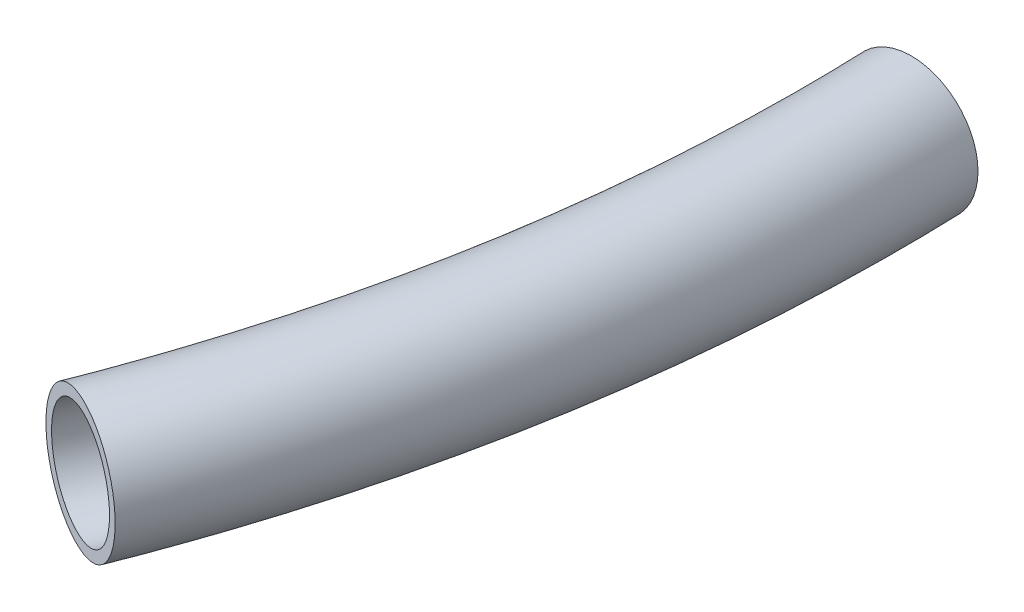
SolidWorks part; units mm, degrees
ref_plane "Front Plane" through (0, 0, 0) normal (0, 0, 1) x (1, 0, 0)
ref_plane "Top Plane" through (0, 0, 0) normal (0, 1, 0) x (1, 0, 0)
ref_plane "Right Plane" through (0, 0, 0) normal (1, 0, 0) x (0, 0, -1)
sketch "Sketch1" plane through (0, 0, 0) normal (0, 0, 1) x (1, 0, 0)
  circle A0 centre (0, 0) radius 0.622
  circle A1 centre (0, 0) radius 0.5206
  dimension "D1" = 1.244
  dimension "D2" = 1.0412
sketch "Sketch2" plane through (0, 0, 0) normal (0, 1, 0) x (1, 0, 0)
  line L0 (-1.2807, -5.2181) -> (-0.4359, -5.5303)
  line L1 (0.6186, 0) -> (-0.6174, 0)
  line L2 (-0.3594, 0) -> (-0.3594, 0.955)
  line L4 (-0.9159, -3.7446) -> (-0.0308, -3.9603)
  line L5 (-0.6889, -2.2259) -> (0.2332, -2.3491)
  line L6 (0.1626, -2.8371) -> (-0.7475, -2.7262)
  line L7 (-0.5001, 0.955) -> (-0.5001, 0)
  line L8 (-0.6186, -1.2203) -> (0.293, -1.2203)
  line L9 (-0.3594, 0.955) -> (-0.5001, 0.955)
  line L10 (-1.0137, -4.2027) -> (-0.1397, -4.4401)
  line L11 (-0.622, 0) -> (0.622, 0) construction
  line L12 (-0.622, 0) -> (0.622, 0) construction
  line L13 (-1.2807, -5.2181) -> (-1.863, -6.8482) construction
  line L14 (-1.0849, -7.6927) -> (-0.5001, 2.9608) construction
  line L17 (-0.5608, -6.8714) -> (-1.6957, -6.4327)
  arc A0 (-0.4359, -5.5303) -> (-0.1397, -4.4401) centre (-16.4821, -0.5853) ccw
  arc A1 (-1.2807, -5.2181) -> (-1.6957, -6.4327) centre (-16.799, -0.5942) cw
  arc A2 (-0.0308, -3.9603) -> (0.1626, -2.8371) centre (-6.8828, -2.2023) ccw
  arc A3 (-0.5608, -2.243) -> (-0.496, -1.2203) centre (-14.6135, -0.839) ccw
  arc A4 (0.2332, -2.3491) -> (0.293, -1.2203) centre (-7.2506, -1.3866) ccw
  arc A5 (-1.0849, -5.2905) -> (-0.7892, -4.2637) centre (-15.1503, -0.6836) ccw
  arc A6 (-0.6889, -2.2259) -> (-0.7475, -2.7262) centre (-16.799, -0.5942) cw
  arc A7 (0.6186, 0) -> (-0.5608, -6.8714) centre (-16.5098, -0.597) cw
  arc A8 (-0.6818, -3.8017) -> (-0.4956, -2.7569) centre (-15.1503, -0.6836) ccw
  arc A9 (-1.1971, -5.249) -> (-0.9046, -4.2323) centre (-14.6135, -0.839) ccw
  arc A10 (-0.6174, 0) -> (-0.6186, -1.2203) centre (-16.799, -0.5942) cw
  arc A11 (-0.9159, -3.7446) -> (-1.0137, -4.2027) centre (-16.799, -0.5942) cw
  arc A12 (-0.799, -3.7731) -> (-0.6196, -2.7418) centre (-14.6135, -0.839) ccw
  arc A13 (-0.4338, -2.26) -> (-0.3594, -1.2203) centre (-15.1503, -0.6836) ccw
  point P44 (0.5831, 0)
sketch "Sketch5" plane through (0, 0, 0) normal (0, 1, 0) x (1, 0, 0)
  line L8 (0.2332, -2.3491) -> (-0.6889, -2.2259)
  line L9 (-0.6186, -1.2203) -> (0.293, -1.2203)
  line L10 (0.6186, 0) -> (-0.6174, 0)
  line L11 (-1.6957, -6.4327) -> (-0.5608, -6.8714)
  line L12 (-0.4359, -5.5303) -> (-1.2807, -5.2181)
  line L13 (-1.0137, -4.2027) -> (-0.1397, -4.4401)
  line L14 (-0.0308, -3.9603) -> (-0.9159, -3.7446)
  line L15 (-0.7475, -2.7262) -> (0.1626, -2.8371)
  line L17 (-1.6957, -6.4327) -> (-0.5608, -6.8714)
  arc A8 (0.2332, -2.3491) -> (0.293, -1.2203) centre (-7.2506, -1.3866) ccw
  arc A9 (-0.6186, -1.2203) -> (-0.6174, 0) centre (-16.799, -0.5942) ccw
  arc A10 (-0.5608, -6.8714) -> (0.6186, 0) centre (-16.5098, -0.597) ccw
  arc A11 (-1.6957, -6.4327) -> (-1.2807, -5.2181) centre (-16.799, -0.5942) ccw
  arc A12 (-0.4359, -5.5303) -> (-0.1397, -4.4401) centre (-16.4821, -0.5853) ccw
  arc A13 (-1.0137, -4.2027) -> (-0.9159, -3.7446) centre (-16.799, -0.5942) ccw
  arc A14 (-0.0308, -3.9603) -> (0.1626, -2.8371) centre (-6.8828, -2.2023) ccw
  arc A15 (-0.7475, -2.7262) -> (-0.6889, -2.2259) centre (-16.799, -0.5942) ccw
  arc A18 (-0.5608, -6.8714) -> (0.6186, 0) centre (-16.5098, -0.597) ccw
  dimension "D1" = 0
sweep "Sweep2" add profiles "Sketch1" path "Sketch2"
sketch "Sketch7" plane through (0, 0, 0) normal (0, 1, 0) x (1, 0, 0)
  line L3 (-1.2807, -5.2181) -> (-1.4555, -5.1535)
  line L4 (-1.4555, -5.1535) -> (-1.1748, -4.1203)
  line L5 (-1.1748, -4.1203) -> (-1.0137, -4.2027)
  line L6 (-0.9159, -3.7446) -> (-1.1749, -3.6815)
  line L7 (-1.1749, -3.6815) -> (-1.0177, -2.665)
  line L8 (0.2332, -2.3491) -> (-0.6889, -2.2259)
  line L9 (-0.6186, -1.2203) -> (0.293, -1.2203)
  line L10 (0.6186, 0) -> (-0.6174, 0)
  line L11 (-1.6957, -6.4327) -> (-0.5608, -6.8714)
  line L12 (-0.4359, -5.5303) -> (-1.2807, -5.2181)
  line L13 (-1.0137, -4.2027) -> (-0.1397, -4.4401)
  line L14 (-0.0308, -3.9603) -> (-0.9159, -3.7446)
  line L15 (-0.7475, -2.7262) -> (0.1626, -2.8371)
  line L16 (0.2332, -2.3491) -> (-0.6889, -2.2259)
  line L17 (-0.6186, -1.2203) -> (0.293, -1.2203)
  line L18 (-1.0177, -2.665) -> (-0.7475, -2.7262)
  line L19 (-0.6889, -2.2259) -> (-0.8846, -2.2259)
  line L20 (-0.4359, -5.5303) -> (-1.2807, -5.2181)
  line L21 (-1.0137, -4.2027) -> (-0.1397, -4.4401)
  line L22 (-0.0308, -3.9603) -> (-0.9159, -3.7446)
  line L23 (-0.7475, -2.7262) -> (0.1626, -2.8371)
  line L24 (-0.8846, -2.2259) -> (-0.7426, -1.1634)
  line L25 (-0.7426, -1.1634) -> (-0.6186, -1.2203)
  line L34 (-1.6957, -6.4327) -> (-0.5608, -6.8714)
  arc A8 (0.2332, -2.3491) -> (0.293, -1.2203) centre (-7.2506, -1.3866) ccw
  arc A9 (-0.6186, -1.2203) -> (-0.6174, 0) centre (-16.799, -0.5942) ccw
  arc A10 (-0.5608, -6.8714) -> (0.6186, 0) centre (-16.5098, -0.597) ccw
  arc A11 (-1.6957, -6.4327) -> (-1.2807, -5.2181) centre (-16.799, -0.5942) ccw
  arc A12 (-0.4359, -5.5303) -> (-0.1397, -4.4401) centre (-16.4821, -0.5853) ccw
  arc A13 (-1.0137, -4.2027) -> (-0.9159, -3.7446) centre (-16.799, -0.5942) ccw
  arc A14 (-0.0308, -3.9603) -> (0.1626, -2.8371) centre (-6.8828, -2.2023) ccw
  arc A15 (-0.7475, -2.7262) -> (-0.6889, -2.2259) centre (-16.799, -0.5942) ccw
  arc A16 (0.2332, -2.3491) -> (0.293, -1.2203) centre (-7.2506, -1.3866) ccw
  arc A20 (-0.4359, -5.5303) -> (-0.1397, -4.4401) centre (-16.4821, -0.5853) ccw
  arc A22 (-0.0308, -3.9603) -> (0.1626, -2.8371) centre (-6.8828, -2.2023) ccw
  dimension "D1" = 0
extrude "Cut-Extrude1" cut sketch "Sketch7" against normal through all and the other way through all rebuild error yes
ref_plane "Plane1" through (-0.6606, 0, -0.0363) normal (0.9985, 0, 0.0548) x (0.0548, 0, -0.9985)
sketch "Sketch9" plane through (-0.6606, 0, -0.0363) normal (0.9985, 0, 0.0548) x (0.0548, 0, -0.9985)
  circle A0 centre (-5.7758, 0) radius 0.2
  spline S0 degree 3 poles (5756.0951, 1621.9735) (-15.2387, -372.4756) (-9.1049, 0.917) (-5.4236, 0.6193) (-5.3923, 0.589) (-5.3378, 0.4785) (-5.3152, 0.3996) (-5.2842, 0.2144) (-5.2758, 0.1074) (-5.2758, -0.1073) (-5.2841, -0.2138) (-5.3151, -0.3991) (-5.3379, -0.4786) (-5.3921, -0.5886) (-5.4233, -0.6192) (-9.0386, -0.9236) (-15.6576, 360.2341) (5657.6128, -1942.8432) knots -14.422171 -14.422171 -14.422171 -14.422171 0.125 0.125 0.25 0.25 0.375 0.375 0.5 0.5 0.625 0.625 0.75 0.75 0.875 0.875 15.129155 15.129155 15.129155 15.129155 only from (-5.5459, 0.5484) to (-5.5459, -0.5484) construction
  spline S1 degree 3 poles (-5.5459, 0.5484) (-5.5178, 0.5993) (-5.4863, 0.6244) (-5.4236, 0.6193) (-5.3923, 0.589) (-5.3378, 0.4785) (-5.3152, 0.3996) (-5.2842, 0.2144) (-5.2758, 0.1074) (-5.2758, -0.1073) (-5.2841, -0.2138) (-5.3151, -0.3991) (-5.3379, -0.4786) (-5.3921, -0.5886) (-5.4233, -0.6192) (-5.4862, -0.6245) (-5.5178, -0.5993) (-5.5459, -0.5484) knots 0 0 0 0 0.125 0.125 0.25 0.25 0.375 0.375 0.5 0.5 0.625 0.625 0.75 0.75 0.875 0.875 1 1 1 1 construction
  point P4 (-5.2758, 0)
  dimension "D1" = 0.4
  dimension "D2" = 0.5
extrude "Cut-Extrude2" cut sketch "Sketch9" against normal blind 10
equation "\"Ro\"= 0.622mm"
equation "\"H\"= 2"
equation "\"G\"= 0.8"
equation "\"Ang\"=15"
equation "\"Bend_Ang\"= 55"
equation "\"Rad_comp\"=0.3"
equation "\"H_m\"= 0.85"
equation "\"Fillet_inner\"=0.0968091"
equation "\"Taper\"= 0.35"
equation "\"T\"= 0.163"
equation "\"Slit_w\"=0.02"
equation "\"Do\"=8.5mm"
equation "\"Lo\"=10"
equation "\"screw_diam\" = 3.5mm"
equation "\"wheel_Do\"=12.5mm"
equation "\"wheel_thickness\"=4mm"
equation "\"Collet_diameter\"=4.3"
equation "\"clearance\"= 0.5mm"
equation "\"handle_body_width\" = 10mm"
equation "\"finger_diameter\"=35"
equation "\"collet_lid_diameter\"=10"
equation "\"screw_cap_diam\"=5.15"
equation "\"handle_thickness\"=12.5mm"
equation "\"post_hole_diam\"=2"
equation "\"roll_rod_diam\"= 6.5 "
equation "\"roll_rod_length\"=6.6"
equation "\"disc_diam\"=5"
equation "\"disc_width\"=1.5"
equation "\"arm_width\"=5"
equation "\"arm_thickness\"=4.5"
equation "\"wheel_total_diam\"=30"
equation "\"spring_diam\"=4.1"
equation "\"collet_length\" = 18.75mm"
equation "\"tip_length\" = 40mm"
equation "\"cable_tube_OD\"=0.508"
equation "\"cable_OD\" = 0.3mm"
equation "\"Rc\" = 1.45mm"
equation "\"D2@Sketch1\"=(1-\"T\")*\"Ro\"*2"
